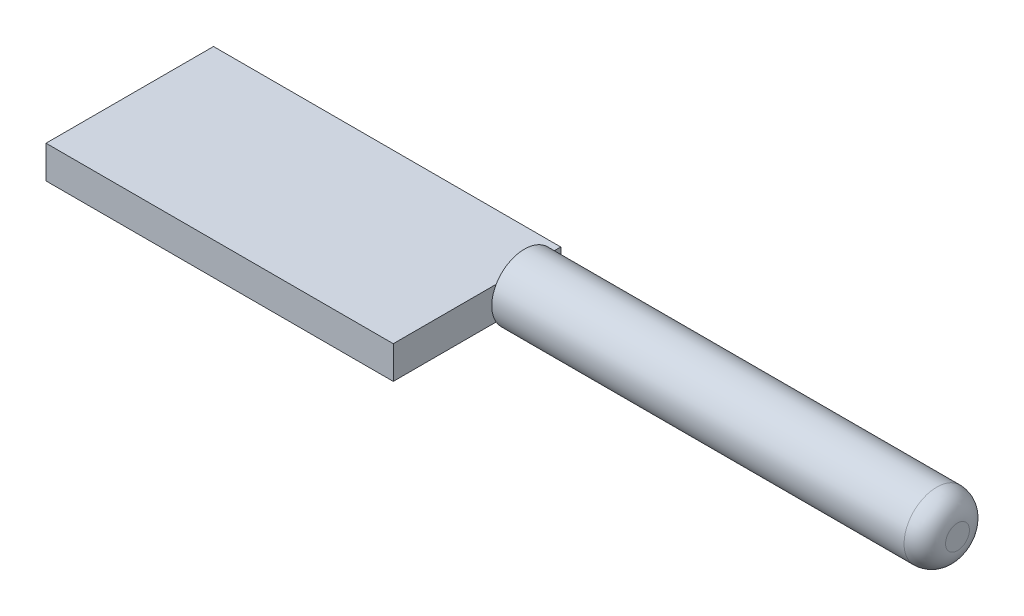
SolidWorks part; units mm, degrees
ref_plane "Front Plane" through (0, 0, 0) normal (0, 0, 1) x (1, 0, 0)
ref_plane "Top Plane" through (0, 0, 0) normal (0, 1, 0) x (1, 0, 0)
ref_plane "Right Plane" through (0, 0, 0) normal (1, 0, 0) x (0, 0, -1)
sketch "Sketch1" plane through (0, 0, 0) normal (0, 1, 0) x (1, 0, 0)
  line L1 (-21.25, -10.25) -> (21.25, -10.25)
  line L2 (-21.25, -10.25) -> (-21.25, 10.25)
  line L3 (-21.25, 10.25) -> (21.25, 10.25)
  line L4 (21.25, -10.25) -> (21.25, 10.25)
  line L5 (-21.25, -10.25) -> (21.25, 10.25) construction
  line L6 (-21.25, 10.25) -> (21.25, -10.25) construction
  point P0 (0, 0)
  dimension "D1" = 20.5
  dimension "D2" = 42.5
extrude "Boss-Extrude1" add sketch "Sketch1" along normal blind 4
sketch "Sketch2" plane through (21.25, 0, 0) normal (1, 0, 0) x (0, 0, -1)
  circle A0 centre (5.8044, 2) radius 4
  point P2 (4.9662, 2.0419)
  point P3 (5.8044, 2)
extrude "Boss-Extrude2" add sketch "Sketch2" along normal blind 53
fillet "Fillet1" radius 2.54 1 edges at (74.25, 2, -9.8044)
